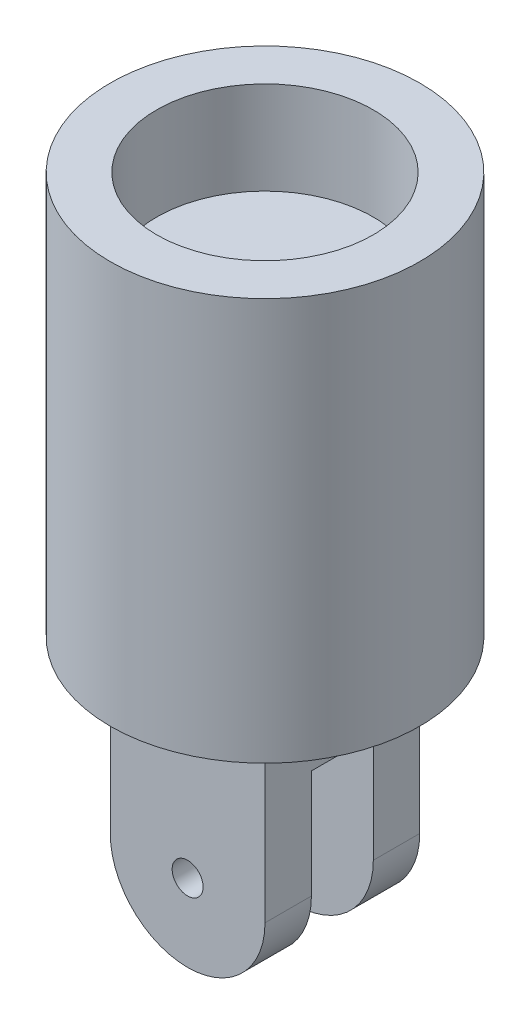
SolidWorks part; units mm, degrees
ref_plane "Front Plane" through (0, 0, 0) normal (0, 0, 1) x (1, 0, 0)
ref_plane "Top Plane" through (0, 0, 0) normal (0, 1, 0) x (1, 0, 0)
ref_plane "Right Plane" through (0, 0, 0) normal (1, 0, 0) x (0, 0, -1)
sketch "Sketch1" plane through (0, 0, 0) normal (0, 1, 0) x (1, 0, 0)
  circle A0 centre (0, 0) radius 5
extrude "Boss-Extrude1" add sketch "Sketch1" along normal blind 13
sketch "Sketch2" plane through (0, 13, 0) normal (0, 1, 0) x (1, 0, 0)
  circle A0 centre (0, 0) radius 3.5
extrude "Cut-Extrude1" cut sketch "Sketch2" against normal blind 3
sketch "Sketch3" plane through (0, 0, 0) normal (0, -1, 0) x (-1, 0, 0)
  line L1 (-2.5, 2.5) -> (2.5, 2.5)
  line L2 (-2.5, 2.5) -> (-2.5, -2.5)
  line L3 (-2.5, -2.5) -> (2.5, -2.5)
  line L4 (2.5, 2.5) -> (2.5, -2.5)
  line L5 (-2.5, 2.5) -> (2.5, -2.5) construction
  line L6 (-2.5, -2.5) -> (2.5, 2.5) construction
  point P0 (0, 0)
  dimension "D1" = 5
  dimension "D2" = 5
extrude "Boss-Extrude2" add sketch "Sketch3" along normal blind 8 contours L2 L3 L4 L1
sketch "Sketch4" plane through (0, -8, 0) normal (0, -1, 0) x (-1, 0, 0)
  line L0 (2.5, 2.5) -> (2.5, -2.5) construction
  line L1 (-2.5, 1) -> (2.5, 1)
  line L2 (-2.5, 1) -> (-2.5, -1)
  line L3 (-2.5, -1) -> (2.5, -1)
  line L4 (2.5, 1) -> (2.5, -1)
  line L5 (-2.5, 1) -> (2.5, -1) construction
  line L6 (-2.5, -1) -> (2.5, 1) construction
  point P0 (0, 0)
  dimension "D1" = 2
  dimension "D2" = 5
extrude "Cut-Extrude2" cut sketch "Sketch4" against normal blind 6
fillet "Fillet2" radius 2.5 4 edges at (-2.5, -8, 1.75) (2.5, -8, 1.75) (2.5, -8, -1.75) (-2.5, -8, -1.75)
sketch "Sketch5" plane through (0, 0, -2.5) normal (0, 0, -1) x (-1, 0, 0)
  circle A0 centre (0, -5.5) radius 0.5
  point P2 (0, 0)
  point P3 (0, 0)
extrude "Cut-Extrude4" cut sketch "Sketch5" against normal through all contours A0
